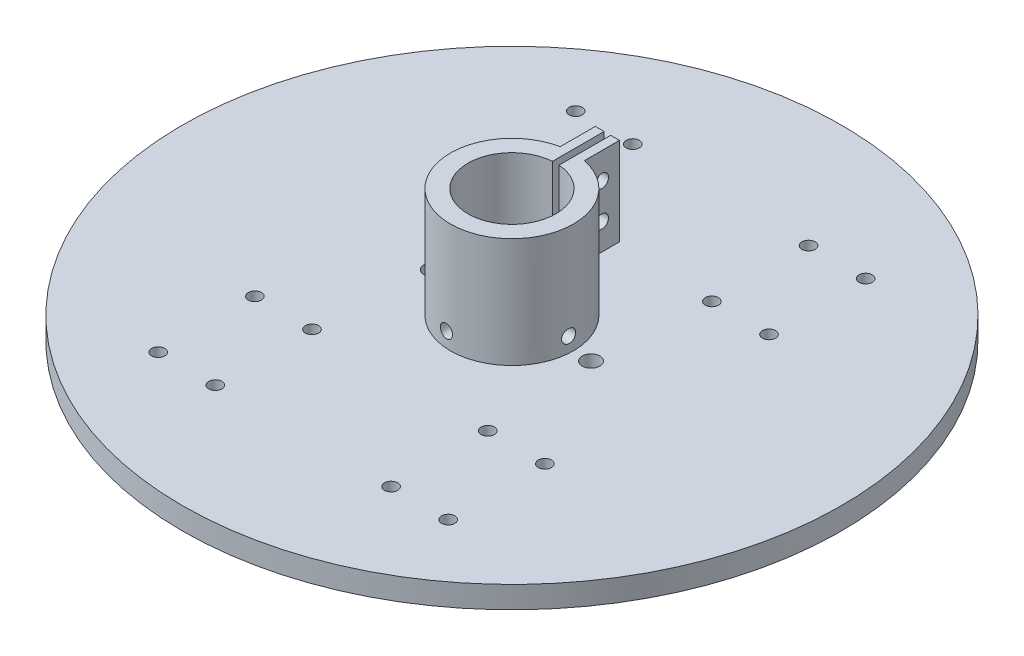
SolidWorks part; units mm, degrees
ref_plane "Front Plane" through (0, 0, 0) normal (0, 0, 1) x (1, 0, 0)
ref_plane "Top Plane" through (0, 0, 0) normal (0, 1, 0) x (1, 0, 0)
ref_plane "Right Plane" through (0, 0, 0) normal (1, 0, 0) x (0, 0, -1)
sketch "Sketch1" plane through (0, 0, 0) normal (0, 1, 0) x (1, 0, 0)
  circle A0 centre (0, 0) radius 75
  dimension "D1" = 150
extrude "Boss-Extrude1" add sketch "Sketch1" along normal blind 5
sketch "Sketch2" plane through (0, 5, 0) normal (0, 1, 0) x (1, 0, 0)
  circle A0 centre (0, 0) radius 14
  circle A1 centre (0, 0) radius 4
  circle A2 centre (0, 0) radius 10
  dimension "D1" = 8
  dimension "D2" = 28
  dimension "D3" = 20
extrude "Boss-Extrude2" add sketch "Sketch2" along normal blind 25 contours A0 A2 | A1 region at (-13.604, 5, 0) region at (0, 5, 0)
sketch "Sketch3" plane through (0, 30, 0) normal (0, 1, 0) x (1, 0, 0)
  circle A0 centre (0, 0) radius 4
  dimension "D1" = 8
extrude "Cut-Extrude1" cut sketch "Sketch3" against normal blind 12
ref_plane "Plane1" through (14, 0, 0) normal (1, 0, 0) x (0, 0, -1)
sketch "Sketch4" plane through (14, 0, 0) normal (1, 0, 0) x (0, 0, -1)
  line L1 (14, 5) -> (-14, 5) construction
  line L2 (14, 5) -> (14, 30) construction
  circle A0 centre (-1, 8.4) radius 1.5
  dimension "D1" = 3
  dimension "D2" = 3.4
  dimension "D3" = 15
extrude "Cut-Extrude2" cut sketch "Sketch4" against normal up to next
ref_plane "Plane2" through (0, 0, 14) normal (0, 0, 1) x (1, 0, 0)
sketch "Sketch5" plane through (0, 0, 14) normal (0, 0, 1) x (1, 0, 0)
  line L0 (14, -13.75) -> (14, 13.75) construction
  line L1 (14, 5) -> (-14, 5) construction
  circle A0 centre (-1, 8.4) radius 1.5
  dimension "D1" = 3
  dimension "D2" = 15
  dimension "D3" = 3.4
extrude "Cut-Extrude3" cut sketch "Sketch5" against normal up to next
sketch "Sketch6" plane through (0, 0, 0) normal (0, -1, 0) x (1, 0, 0)
  line L0 (-106.3466, 0) -> (112.8257, 0) construction
  line L1 (0, 87.2444) -> (0, -91.9362) construction
  circle A0 centre (-18, 0) radius 2
  circle A1 centre (18, 0) radius 2
  dimension "D1" = 18
  dimension "D2" = 18
  dimension "D3" = 4
extrude "Cut-Extrude4" cut sketch "Sketch6" against normal through all
sketch "Sketch7" plane through (0, 0, 0) normal (0, -1, 0) x (1, 0, 0)
  line L0 (0, 78.8593) -> (0, -84.0957) construction
  line L1 (-106.193, 0) -> (115.409, 0) construction
  line L2 (-83.4138, 36.5) -> (98.0235, 36.5) construction
  line L3 (26.5, 95.648) -> (26.5, -42.6819) construction
  circle A0 centre (20, 47.5) radius 1.5
  circle A2 centre (33, 47.5) radius 1.5
  circle A3 centre (20, 25.5) radius 1.5
  circle A4 centre (33, 25.5) radius 1.5
  circle A5 centre (-20, 25.5) radius 1.5
  circle A6 centre (-33, 25.5) radius 1.5
  circle A7 centre (-33, 47.5) radius 1.5
  circle A8 centre (-20, 47.5) radius 1.5
  circle A9 centre (-33, -47.5) radius 1.5
  circle A10 centre (-20, -47.5) radius 1.5
  circle A11 centre (-20, -25.5) radius 1.5
  circle A12 centre (-33, -25.5) radius 1.5
  circle A13 centre (20, -25.5) radius 1.5
  circle A14 centre (20, -47.5) radius 1.5
  circle A15 centre (33, -47.5) radius 1.5
  circle A16 centre (33, -25.5) radius 1.5
  dimension "D1" = 20
  dimension "D2" = 3
  dimension "D3" = 47.5
  dimension "D4" = 36.5
  dimension "D5" = 26.5
extrude "Cut-Extrude5" cut sketch "Sketch7" against normal through all
sketch "Sketch8" plane through (0, 30, 0) normal (0, 1, 0) x (1, 0, 0)
  line L0 (0, 61.0557) -> (0, -64.1976) construction
  line L1 (-56.5525, 0) -> (50.8972, 0) construction
  line L2 (0.75, 13.9799) -> (0.75, 9.9718)
  line L3 (-0.75, 13.9799) -> (-0.75, 9.9718)
  circle A2 centre (0, 0) radius 14 construction
  circle A3 centre (0, 0) radius 10 construction
  arc A4 (0.75, 13.9799) -> (-0.75, 13.9799) centre (0, 0) ccw
  arc A5 (0.75, 9.9718) -> (-0.75, 9.9718) centre (0, 0) ccw
  dimension "D2" = 14
  dimension "D3" = 10
  dimension "D1" = 0.75
extrude "Cut-Extrude6" cut sketch "Sketch8" against normal up to surface (25 mm away) up to face at (-33, 5, 27)
sketch "Sketch9" plane through (0, 30, 0) normal (0, 1, 0) x (1, 0, 0)
  line L0 (0, 20.0372) -> (0, -1.2241) construction
  line L1 (0.75, 13.9799) -> (0.75, 21.7273)
  line L2 (0.75, 21.7273) -> (2.75, 21.7273)
  line L3 (2.75, 21.7273) -> (2.75, 13.7273)
  line L4 (-0.75, 21.7273) -> (-2.75, 21.7273)
  line L5 (-2.75, 21.7273) -> (-2.75, 13.7273)
  line L6 (-0.75, 13.9799) -> (-0.75, 21.7273)
  arc A0 (-0.75, 13.9799) -> (0.75, 13.9799) centre (0, 0) ccw construction
  arc A1 (2.75, 13.7273) -> (0.75, 13.9799) centre (0, 0) ccw
  arc A2 (-2.75, 13.7273) -> (-0.75, 13.9799) centre (0, 0) cw
  dimension "D1" = 2
  dimension "D2" = 8
extrude "Boss-Extrude3" add sketch "Sketch9" against normal blind 20
sketch "Sketch10" plane through (2.75, 0, 0) normal (1, 0, 0) x (0, 0, -1)
  line L0 (13.7273, 10) -> (21.7273, 10) construction
  line L1 (13.7273, 30) -> (21.7273, 30) construction
  line L2 (13.7273, 10) -> (13.7273, 30) construction
  circle A0 centre (17.7273, 24) radius 1.5
  circle A1 centre (17.7273, 16) radius 1.5
  point P4 (0, 0)
  dimension "D1" = 3
  dimension "D2" = 6
  dimension "D3" = 6
  dimension "D4" = 4
extrude "Cut-Extrude7" cut sketch "Sketch10" against normal through all
